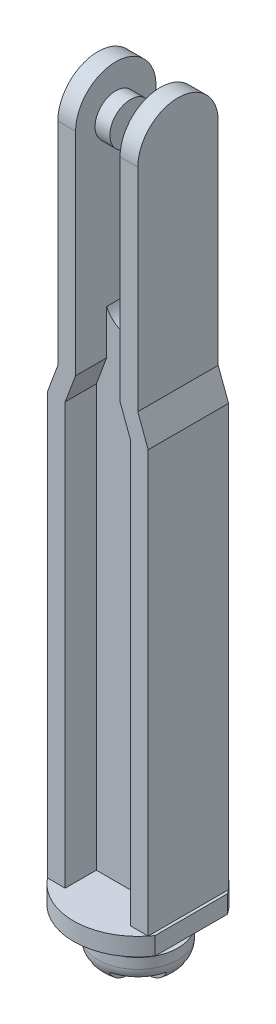
SolidWorks part; units mm, degrees
ref_plane "Front Plane" through (0, 0, 0) normal (0, 0, 1) x (1, 0, 0)
ref_plane "Top Plane" through (0, 0, 0) normal (0, 1, 0) x (1, 0, 0)
ref_plane "Right Plane" through (0, 0, 0) normal (1, 0, 0) x (0, 0, -1)
sketch "Sketch1" plane through (0, 0, 0) normal (0, 1, 0) x (1, 0, 0)
  circle A0 centre (0, 0) radius 4.35
  dimension "D1" = 8.7
extrude "Boss-Extrude1" add sketch "Sketch1" along normal blind 1.2
sketch "Sketch2" plane through (0, 0, 0) normal (0, -1, 0) x (1, 0, 0)
  line L1 (2, -0.6) -> (-2, -0.6)
  line L2 (2, -0.6) -> (2, 0.6)
  line L3 (2, 0.6) -> (-2, 0.6)
  line L4 (-2, -0.6) -> (-2, 0.6)
  line L5 (2, -0.6) -> (-2, 0.6) construction
  line L6 (2, 0.6) -> (-2, -0.6) construction
  line L7 (0.6, -2) -> (-0.6, -2)
  line L8 (0.6, -2) -> (0.6, 2)
  line L9 (0.6, 2) -> (-0.6, 2)
  line L10 (-0.6, -2) -> (-0.6, 2)
  line L11 (0.6, -2) -> (-0.6, 2) construction
  line L12 (0.6, 2) -> (-0.6, -2) construction
  point P0 (0, 0)
  point P6 (0, 0)
  dimension "D1" = 1.2
  dimension "D2" = 4
extrude "Boss-Extrude2" add sketch "Sketch2" along normal blind 1.2 contours L1 L10 L3 L4 | L10 L7 L8 L1 | L8 L1 L2 L3 | L10 L3 L8 L9 | L10 L1 L8 L3 region at (1.3, 0, 0) region at (0, 0, -1.3) region at (0, 0, 0) region at (-1.3, 0, 0) region at (0, 0, 1.3)
sketch "Sketch3" plane through (0, -1.2, 0) normal (0, -1, 0) x (1, 0, 0)
  circle A0 centre (0, 0) radius 2.7
  dimension "D1" = 5.4
extrude "Boss-Extrude3" add sketch "Sketch3" along normal blind 1.2
sketch "Sketch4" plane through (0, -2.4, 0) normal (0, -1, 0) x (1, 0, 0)
  line L1 (2.7, -0.6) -> (-2.7, -0.6)
  line L2 (2.7, -0.6) -> (2.7, 0.6)
  line L3 (2.7, 0.6) -> (-2.7, 0.6)
  line L4 (-2.7, -0.6) -> (-2.7, 0.6)
  line L5 (2.7, -0.6) -> (-2.7, 0.6) construction
  line L6 (2.7, 0.6) -> (-2.7, -0.6) construction
  line L7 (0.6, -2.7) -> (-0.6, -2.7)
  line L8 (0.6, -2.7) -> (0.6, 2.7)
  line L9 (0.6, 2.7) -> (-0.6, 2.7)
  line L10 (-0.6, -2.7) -> (-0.6, 2.7)
  line L11 (0.6, -2.7) -> (-0.6, 2.7) construction
  line L12 (0.6, 2.7) -> (-0.6, -2.7) construction
  circle A0 centre (0, 0) radius 2.7 construction
  point P0 (0, 0)
  point P6 (0, 0)
  circle M9 centre (0, 0) radius 2.7
  dimension "D1" = 1.2
extrude "Boss-Extrude4" add sketch "Sketch4" along normal blind 0.8 contours L10 L8 L1 M9 | L1 L10 L3 M9 | L8 L1 L3 M9 | L10 L3 L8 M9 | L10 L1 L8 L3 region at (1.6389, -2.4, 0) region at (0, -2.4, -1.6389) region at (0, -2.4, 0) region at (-1.6389, -2.4, 0) region at (0, -2.4, 1.6389)
fillet "Fillet1" radius 1.3 1 edges at (-2.7, -3.2, 0)
sketch "Sketch5" plane through (0, 1.2, 0) normal (0, 1, 0) x (1, 0, 0)
  line L1 (3.6, -5) -> (-3.6, -5) construction
  line L2 (3.6, -5) -> (3.6, 5) construction
  line L3 (3.6, 5) -> (-3.6, 5) construction
  line L4 (-3.6, -5) -> (-3.6, 5) construction
  line L5 (3.6, -5) -> (-3.6, 5) construction
  line L6 (3.6, 5) -> (-3.6, -5) construction
  line L7 (-3.6, 5) -> (-4.6, 5)
  line L8 (-3.6, 5) -> (-3.6, -5)
  line L9 (-3.6, -5) -> (-4.6, -5)
  line L10 (-4.6, 5) -> (-4.6, -5)
  line L11 (3.6, 5) -> (4.6, 5)
  line L12 (3.6, 5) -> (3.6, -5)
  line L13 (3.6, -5) -> (4.6, -5)
  line L14 (4.6, 5) -> (4.6, -5)
  point P0 (0, 0)
  dimension "D1" = 7.2
  dimension "D2" = 10
  dimension "D3" = 1
extrude "Cut-Extrude1" cut sketch "Sketch5" against normal blind 1.2
sketch "Sketch6" plane through (0, 1.2, 0) normal (0, 1, 0) x (1, 0, 0)
  line L0 (-3.6, -2.4418) -> (-3.6, 2.4418) construction
  line L1 (3.4, -2.7134) -> (-3.4, -2.7134)
  line L2 (3.4, -2.7134) -> (3.4, 2.7134)
  line L3 (3.4, 2.7134) -> (-3.4, 2.7134)
  line L4 (-3.4, -2.7134) -> (-3.4, 2.7134)
  line L5 (3.4, -2.7134) -> (-3.4, 2.7134) construction
  line L6 (3.4, 2.7134) -> (-3.4, -2.7134) construction
  arc A0 (-3.6, -2.4418) -> (3.6, -2.4418) centre (0, 0) ccw construction
  arc A1 (3.6, 2.4418) -> (-3.6, 2.4418) centre (0, 0) ccw construction
  point P0 (0, 0)
  arc M6 (-3.6, -2.4418) -> (3.6, -2.4418) centre (0, 0) ccw
  arc M8 (3.6, 2.4418) -> (-3.6, 2.4418) centre (0, 0) ccw
  dimension "D1" = 0.2
extrude "Boss-Extrude5" add sketch "Sketch6" along normal blind 47.3 contours L4 L1 L2 L3 M6 M8 region at (0, 1.2, 0)
sketch "Sketch7" plane through (3.4, 0, 0) normal (1, 0, 0) x (0, 0, -1)
  line L0 (2.7134, 48.5) -> (2.7134, 1.2) construction
  line L1 (-2.7134, 48.5) -> (2.7134, 48.5)
  line L2 (-2.7134, 48.5) -> (-2.7134, 31.5)
  line L3 (-2.7134, 31.5) -> (2.7134, 31.5)
  line L4 (2.7134, 48.5) -> (2.7134, 31.5)
  dimension "D1" = 17
extrude "Cut-Extrude2" cut sketch "Sketch7" against normal blind 0.7
sketch "Sketch8" plane through (0, 0, -2.7134) normal (0, 0, -1) x (-1, 0, 0)
  line L0 (-2.7, 31.5) -> (-3.4, 29.6265)
  line L1 (-3.4, 31.5) -> (-3.4, 1.2) construction
  line L2 (-3.4, 29.6265) -> (-3.4, 31.5)
  line L3 (-3.4, 31.5) -> (-2.7, 31.5)
  dimension "D1" = 2
extrude "Cut-Extrude3" cut sketch "Sketch8" against normal up to surface (5.4268 mm away) up to face at (0.9, 27.0667, 2.7134)
sketch "Sketch9" plane through (0, 0, 2.7134) normal (0, 0, 1) x (1, 0, 0)
  line L1 (3.4, 1.2) -> (-3.4, 1.2) construction
  line L2 (-2.2, 1.2) -> (2.2, 1.2)
  line L3 (-2.2, 1.2) -> (-2.2, 29.6265)
  line L4 (-2.2, 29.6265) -> (2.2, 29.6265)
  line L5 (2.2, 1.2) -> (2.2, 29.6265)
  line L10 (0, 1.2) -> (0, 50001.2) construction
  line L11 (3.4, 1.2) -> (-3.4, 1.2) construction
  line L14 (3.4, 29.6265) -> (-49996.6, 29.6265) construction
  point P10 (0, 1.2)
  dimension "D1" = 4.4
extrude "Cut-Extrude4" cut sketch "Sketch9" against normal blind 2.1
sketch "Sketch11" plane through (0, 0, 2.7134) normal (0, 0, 1) x (1, 0, 0)
  line L0 (2.7, 48.5) -> (-3.4, 48.5) construction
  line L1 (1.5, 48.5) -> (-1.5, 48.5)
  line L2 (1.5, 48.5) -> (1.5, 29.6265)
  line L3 (1.5, 29.6265) -> (-1.5, 29.6265)
  line L4 (-1.5, 48.5) -> (-1.5, 29.6265)
  line L5 (2.2, 29.6265) -> (-2.2, 29.6265) construction
  line L6 (0, 1.2) -> (0, 50001.2) construction
  line L7 (-2.2, 1.2) -> (2.2, 1.2) construction
  point P13 (0, 1.2)
  dimension "D1" = 3
extrude "Cut-Extrude5" cut sketch "Sketch11" against normal blind 2.1
sketch "Sketch12" plane through (0, 0, 2.7134) normal (0, 0, 1) x (1, 0, 0)
  line L0 (2.2, 29.6265) -> (1.5, 31.5)
  line L1 (1.5, 29.6265) -> (1.5, 48.5) construction
  line L2 (1.5, 31.5) -> (1.5, 29.6265)
  line L3 (1.5, 29.6265) -> (2.2, 29.6265)
extrude "Cut-Extrude6" cut sketch "Sketch12" against normal blind 2.1
mirror "Mirror1" about plane through (0, 0, 0) normal (1, 0, 0) of "Cut-Extrude3", "Cut-Extrude2", "Cut-Extrude6"
mirror "Mirror3" about plane through (0, 0, 0) normal (0, 0, 1) of "Cut-Extrude6", "Cut-Extrude5", "Cut-Extrude4"
sketch "Sketch13" plane through (0, 0, -2.7134) normal (0, 0, -1) x (-1, 0, 0)
  line L0 (2.2, 29.6265) -> (1.5, 31.5)
  line L1 (1.5, 48.5) -> (1.5, 29.6265) construction
  line L2 (1.5, 31.5) -> (1.5, 29.6265)
  line L3 (1.5, 29.6265) -> (2.2, 29.6265)
extrude "Cut-Extrude7" cut sketch "Sketch13" against normal blind 2.1
sketch "Sketch14" plane through (0, 0, 0.6134) normal (0, 0, 1) x (1, 0, 0)
  line L0 (-1.5, 31.5) -> (49998.5, 31.5) construction
  line L1 (1.5, 31.5) -> (1.5, 48.5) construction
  line L2 (-1.5, 48.5) -> (1.5, 48.5)
  line L3 (-1.5, 48.5) -> (-1.5, 34.5)
  line L4 (-1.5, 34.5) -> (1.5, 34.5)
  line L5 (1.5, 48.5) -> (1.5, 34.5)
  line L7 (-1.5, 34.5) -> (1.5, 34.5) construction
  line L8 (-1.5, 34.5) -> (-1.5, 33.5) construction
  line L9 (-1.5, 33.5) -> (1.5, 33.5) construction
  line L10 (1.5, 34.5) -> (1.5, 33.5) construction
  arc A0 (1.5, 34.5) -> (-1.5, 34.5) centre (0, 35.125) cw
  line M11 (1.5, 31.5) -> (1.5, 48.5)
  line M12 (1.5, 48.5) -> (-1.5, 48.5)
  line M13 (-1.5, 48.5) -> (-1.5, 31.5)
  dimension "D1" = 3
  dimension "D2" = 1
extrude "Cut-Extrude8" cut sketch "Sketch14" against normal up to surface (1.2268 mm away) contours L4 M13 M11 M12 | A0 L4 region at (0, 41.5, 0.6134) region at (0, 34.0871, 0.6134)
sketch "Sketch15" plane through (2.7, 0, 0) normal (1, 0, 0) x (0, 0, -1)
  line L0 (2.7134, 31.5) -> (2.7134, 48.5) construction
  line L1 (-2.7134, 48.5) -> (2.7134, 48.5) construction
  line L2 (-2.7134, 48.5) -> (-2.7134, 45.8) construction
  line L3 (-2.7134, 45.8) -> (2.7134, 45.8) construction
  line L4 (2.7134, 48.5) -> (2.7134, 45.8) construction
  line L5 (-2.7134, 45.8) -> (-2.7134, 48.5)
  line L6 (-2.7134, 48.5) -> (2.7134, 48.5)
  line L7 (2.7134, 48.5) -> (2.7134, 45.8)
  arc A0 (-2.7134, 45.8) -> (2.7134, 45.8) centre (0, 45.7866) cw
  line M3 (-2.7134, 48.5) -> (-2.7134, 31.5)
  line M5 (2.7134, 31.5) -> (2.7134, 48.5)
  line M6 (2.7134, 48.5) -> (-2.7134, 48.5)
  dimension "D1" = 2.7
extrude "Cut-Extrude10" cut sketch "Sketch15" against normal blind 1.2 contours A0 L6 M3 | A0 M6 M5 region at (2.7, 47.894, -2.1073) region at (2.7, 47.894, 2.1073)
mirror "Mirror10" about plane through (0, 0, 0) normal (1, 0, 0) of "Cut-Extrude10"
sketch "Sketch17" plane through (-1.5, 0, 0) normal (1, 0, 0) x (0, 0, -1)
  line L0 (0, 48.5) -> (50000, 48.5) construction
  circle A0 centre (0, 45.4) radius 1.4
  arc A1 (2.7134, 45.8) -> (-2.7134, 45.8) centre (0, 45.7866) ccw construction
  point P7 (0, 48.5)
  dimension "D1" = 2.8
  dimension "D2" = 3.1
extrude "Boss-Extrude6" add sketch "Sketch17" along normal blind 1
mirror "Mirror11" about plane through (0, 0, 0) normal (1, 0, 0) of "Boss-Extrude6"
